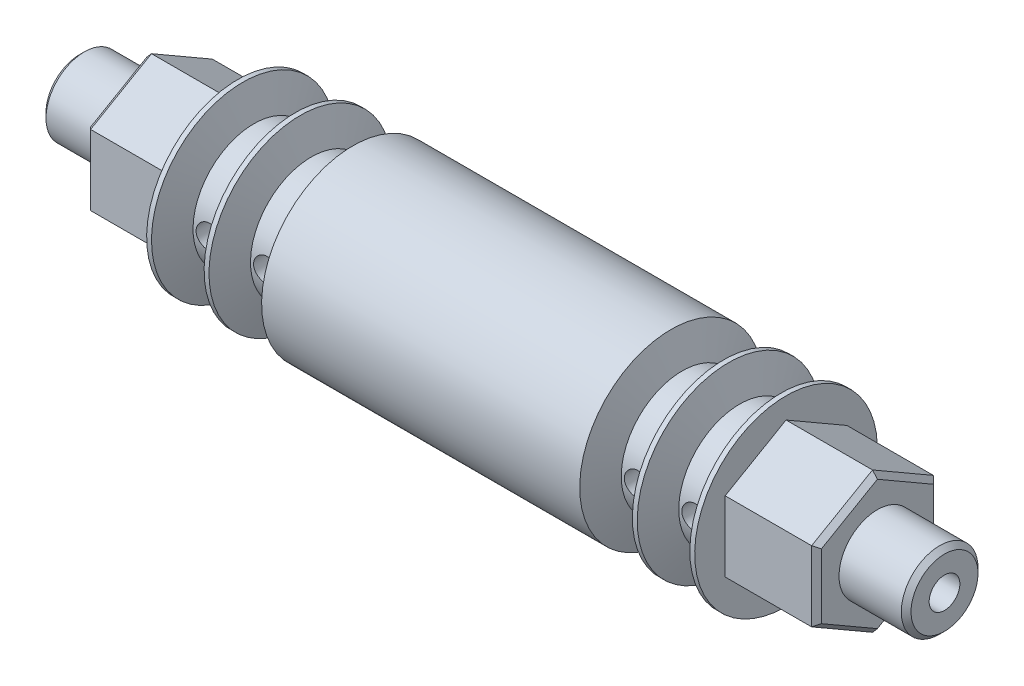
SolidWorks part; units mm, degrees
ref_plane "Front Plane" through (0, 0, 0) normal (0, 0, 1) x (1, 0, 0)
ref_plane "Top Plane" through (0, 0, 0) normal (0, 1, 0) x (1, 0, 0)
ref_plane "Right Plane" through (0, 0, 0) normal (1, 0, 0) x (0, 0, -1)
sketch "Sketch1" plane through (0, 0, 0) normal (0, 0, 1) x (1, 0, 0)
  line L0 (-38.1, 0) -> (38.1, 0) construction
  line L1 (-28.067, 9.525) -> (-26.9114, 6.35)
  line L2 (-26.9114, 6.35) -> (-23.7364, 6.35)
  line L3 (-23.7364, 6.35) -> (-22.5808, 9.525)
  line L4 (-22.5808, 9.525) -> (-22.0728, 9.525)
  line L5 (-22.0728, 9.525) -> (-20.9172, 6.35)
  line L6 (-20.9172, 6.35) -> (-17.7422, 6.35)
  line L7 (-17.7422, 6.35) -> (-16.5866, 9.525)
  line L8 (0, 0) -> (0, 25.6809) construction
  line L9 (-16.5866, 9.525) -> (0, 9.525)
  line L10 (-22.3268, 9.525) -> (-22.3268, 0) construction
  line L11 (-28.575, 9.525) -> (-28.575, 4.254)
  line L12 (-28.575, 4.254) -> (-38.1, 4.254)
  line L13 (-38.1, 4.254) -> (-38.1, 4)
  line L14 (-38.1, 0) -> (-28.575, 0)
  line L15 (-28.575, 0) -> (0, 0)
  line L16 (-28.067, 9.525) -> (-28.575, 9.525)
  line L17 (0, 0) -> (0, 9.525)
  line L18 (-38.1, 0) -> (-38.1, -4) construction
  line L19 (-28.575, 4.254) -> (-28.575, 0) construction
  line L20 (-45.1, 4) -> (-45.1, 0)
  line L21 (-45.1, 4) -> (-38.1, 4)
  line L22 (-45.1, 0) -> (-45.1, -4) construction
  line L23 (-38.1, 4) -> (-38.1, 0) construction
  line L24 (-38.1, 0) -> (-45.1, 0)
  line L25 (-45.1, 1.6) -> (-35.275, 1.6)
  line L26 (-35.275, 1.6) -> (-33.675, 0)
  line L27 (-45.1, 1.6) -> (-45.1, -1.6) construction
  line L28 (-48.275, -1.5) -> (-35.275, -1.5) construction
  line L29 (-48.275, -1.5) -> (-48.275, 1.5) construction
  line L30 (-48.275, 1.5) -> (-35.275, 1.5) construction
  line L31 (-35.275, -1.5) -> (-35.275, 1.5) construction
  line L32 (-48.275, -1.5) -> (-35.275, 1.5) construction
  line L33 (-48.275, 1.5) -> (-35.275, -1.5) construction
  point P27 (-41.775, 0)
  point P33 (0, 0)
  point P34 (-45.1, 6.2363)
  point P35 (0, 0)
  point P36 (0, 0)
  point P38 (0, 0)
  point P39 (-43.8856, 4.6883)
  point P40 (-45.1, 0)
  point P41 (-43.3356, 4.8198)
  point P42 (0, 0)
  point P43 (0, 0)
  dimension "D2" = 3.175
  dimension "D3" = 3.175
  dimension "D4" = 70
  dimension "D6" = 3.175
  dimension "D5" = 0.508
  dimension "D7" = 3.175
  dimension "D8" = 0.508
  dimension "D11" = 9.525
  dimension "D12" = 8
  dimension "D13" = 7
  dimension "D10" = 0.254
  dimension "D9" = 76.2
  dimension "D14" = 9.525
  dimension "D15" = 13
  dimension "D16" = 3
  dimension "D17" = 3.175
  dimension "D18" = 45
  dimension "D19" = 3.2
revolve "Revolve1" add sketch "Sketch1" angle 360 about L0 region at (-17.2661, 4.0615, 0)
sketch "Sketch4" plane through (-28.575, 0, 0) normal (-1, 0, 0) x (0, 0, 1)
  line L1 (0, 7.3323) -> (-6.35, 3.6662)
  line L2 (-6.35, 3.6662) -> (-6.35, -3.6662)
  line L3 (-6.35, -3.6662) -> (0, -7.3323)
  line L4 (0, -7.3323) -> (6.35, -3.6662)
  line L5 (6.35, -3.6662) -> (6.35, 3.6662)
  line L6 (6.35, 3.6662) -> (0, 7.3323)
  circle A0 centre (0, 0) radius 6.35 construction
  dimension "D1" = 12.7
extrude "Boss-Extrude4" add sketch "Sketch4" along normal up to surface (9.525 mm away) up to face at (-38.1, -4, 0)
sketch "Sketch6" plane through (0, 0, 0) normal (0, 0, 1) x (1, 0, 0)
  line L0 (-25.3239, 6.35) -> (-25.3239, 0) construction
  line L1 (-26.9114, 6.35) -> (-23.7364, 6.35) construction
  line L2 (-19.3297, 6.35) -> (-19.3297, 0) construction
  line L3 (-20.9172, 6.35) -> (-17.7422, 6.35) construction
  line L4 (-28.575, 0) -> (0, 0) construction
  circle A0 centre (-25.3239, 0) radius 1.27
  circle A1 centre (-19.3297, 0) radius 1.27
  dimension "D1" = 2.54
extrude "Cut-Extrude1" cut sketch "Sketch6" against normal through all both and the other way through all
chamfer "Chamfer2" distance 0.508 angle 45 6 edges at (-38.1, 5.4993, 3.175) (-38.1, 0, 6.35) (-38.1, -5.4993, 3.175) (-38.1, -5.4993, -3.175) (-38.1, 0, -6.35) (-38.1, 5.4993, -3.175)
chamfer "Chamfer3" distance 0.508 angle 45 1 edges at (-45.1, -4, 0)
mirror "Mirror2" about plane through (0, 0, 0) normal (1, 0, 0) of bodies 107
equation "\"D12@Sketch1\"=8mm"
equation "\"D19@Sketch1\"=3.2mm"
